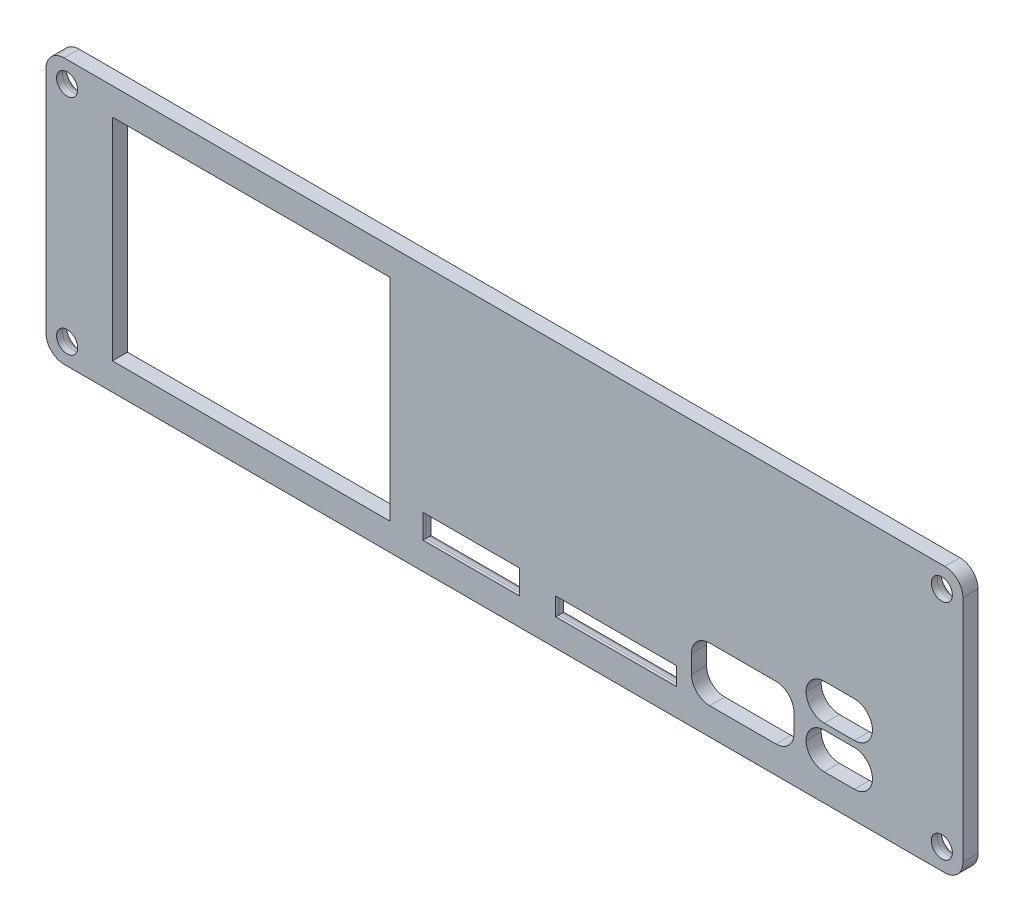
SolidWorks part; units mm, degrees
ref_plane "Front Plane" through (0, 0, 0) normal (0, 0, 1) x (1, 0, 0)
ref_plane "Top Plane" through (0, 0, 0) normal (0, 1, 0) x (1, 0, 0)
ref_plane "Right Plane" through (0, 0, 0) normal (1, 0, 0) x (0, 0, -1)
sketch "Sketch1" plane through (0, 0, 0) normal (0, 0, 1) x (1, 0, 0)
  line L1 (76, -22) -> (-76, -22)
  line L2 (76, -22) -> (76, 22)
  line L3 (76, 22) -> (-76, 22)
  line L4 (-76, -22) -> (-76, 22)
  line L5 (76, -22) -> (-76, 22) construction
  line L6 (76, 22) -> (-76, -22) construction
  point P0 (0, 0)
  dimension "D1" = 152
  dimension "D2" = 44
extrude "main_body" add sketch "Sketch1" along normal blind 2.5
fillet "body_corners" radius 3 4 edges at (-76, -22, 1.25) (76, -22, 1.25) (76, 22, 1.25) (-76, 22, 1.25)
sketch "Sketch2" plane through (0, 0, 2.5) normal (0, 0, 1) x (1, 0, 0)
  line L0 (-76, 18.5) -> (76, 18.5) construction
  line L1 (-76, 19) -> (-76, -19) construction
  line L2 (76, -19) -> (76, 19) construction
  line L3 (-72.5, 22) -> (-72.5, -22) construction
  line L4 (-76, -18.5) -> (76, -18.5) construction
  line L8 (73, 22) -> (-73, 22) construction
  line L9 (72.5, 22) -> (72.5, -22) construction
  line L10 (-73, -22) -> (73, -22) construction
  circle A1 centre (-72.5, -18.5) radius 1.75
  circle A2 centre (72.5, 18.5) radius 1.75
  circle A3 centre (72.5, -18.5) radius 1.75
  circle A4 centre (-72.5, 18.5) radius 1.75
  dimension "D5" = 3.5
  dimension "D6" = 3.5
  dimension "D7" = 3.5
  dimension "D8" = 3.5
  dimension "D1" = 3.5
  dimension "D2" = 3.5
  dimension "D3" = 3.5
  dimension "D4" = 3.5
extrude "mounting_holes" cut sketch "Sketch2" against normal through all
fillet "bolt_heads" radius 1.5 4 edges at (-70.75, -18.5, 0) (-70.75, 18.5, 0) (74.25, -18.5, 0) (74.25, 18.5, 0)
sketch "Sketch3" plane through (0, 0, 2.5) normal (0, 0, 1) x (1, 0, 0)
  line L0 (-76, 5) -> (76, 5) construction
  line L1 (-76, 19) -> (-76, -19) construction
  line L2 (76, -19) -> (76, 19) construction
  line L3 (73, 22) -> (-73, 22) construction
  line L4 (-73, -22) -> (73, -22) construction
  line L5 (0, 22) -> (0, -22) construction
  line L6 (76, -19) -> (76, 19) construction
  line L7 (-65, 17.5) -> (-19, 17.5)
  line L8 (50, -4.5) -> (61, -4.5)
  line L9 (-65, 17.5) -> (-65, -17.5)
  line L10 (50, -4.5) -> (50, -10.5)
  line L11 (50, -10.5) -> (61, -10.5)
  line L12 (-65, -17.5) -> (-19, -17.5)
  line L13 (61, -4.5) -> (61, -10.5)
  line L14 (50, -4.5) -> (61, -10.5) construction
  line L15 (-19, 17.5) -> (-19, -17.5)
  line L16 (50, -10.5) -> (61, -4.5) construction
  line L17 (31, -8.5) -> (48, -8.5)
  line L18 (31, -8.5) -> (31, -17.5)
  line L19 (31, -17.5) -> (48, -17.5)
  line L20 (48, -8.5) -> (48, -17.5)
  line L21 (31, -8.5) -> (48, -17.5) construction
  line L22 (31, -17.5) -> (48, -8.5) construction
  line L23 (50, -11.5) -> (61, -11.5)
  line L24 (50, -11.5) -> (50, -17.5)
  line L25 (50, -17.5) -> (61, -17.5)
  line L26 (61, -11.5) -> (61, -17.5)
  line L27 (50, -11.5) -> (61, -17.5) construction
  line L28 (50, -17.5) -> (61, -11.5) construction
  line L29 (8.5, -14.5) -> (28.5, -14.5)
  line L30 (8.5, -14.5) -> (8.5, -17.5)
  line L31 (8.5, -17.5) -> (28.5, -17.5)
  line L32 (28.5, -14.5) -> (28.5, -17.5)
  line L33 (8.5, -14.5) -> (28.5, -17.5) construction
  line L34 (8.5, -17.5) -> (28.5, -14.5) construction
  line L35 (-13.5, -13.5) -> (2.5, -13.5)
  line L36 (-13.5, -13.5) -> (-13.5, -17.5)
  line L37 (-13.5, -17.5) -> (2.5, -17.5)
  line L38 (2.5, -13.5) -> (2.5, -17.5)
  line L39 (-13.5, -13.5) -> (2.5, -17.5) construction
  line L40 (-13.5, -17.5) -> (2.5, -13.5) construction
  line L41 (-65, 17.5) -> (-19, -17.5) construction
  line L42 (-65, -17.5) -> (-19, 17.5) construction
  line L43 (-76, 19) -> (-76, -19) construction
  line L44 (-73, -22) -> (73, -22) construction
  point P12 (-42, 0)
  point P15 (-5.5, -15.5)
  point P34 (55.5, -14.5)
  point P36 (55.5, -7.5)
  point P41 (39.5, -13)
  point P49 (55.5, -17.5)
  point P51 (18.5, -16)
  dimension "D7" = 73.5
  dimension "D8" = 4.5
  dimension "D9" = 4
  dimension "D10" = 16
  dimension "D11" = 46
  dimension "D12" = 47.5
  dimension "D13" = 6
  dimension "D14" = 11
  dimension "D15" = 28
  dimension "D1" = 17
  dimension "D4" = 11
  dimension "D5" = 4.5
  dimension "D6" = 35
  dimension "D16" = 4.5
  dimension "D17" = 15
  dimension "D18" = 15
  dimension "D19" = 11
  dimension "D20" = 6
  dimension "D21" = 17
  dimension "D22" = 9
  dimension "D25" = 11.5
  dimension "D26" = 4.5
  dimension "D28" = 4.5
  dimension "D30" = 3
  dimension "D31" = 20
extrude "connectors" cut sketch "Sketch3" against normal through all
fillet "usb_host_corners" radius 3 4 edges at (48, -17.5, 1.25) (48, -8.5, 1.25) (31, -17.5, 1.25) (31, -8.5, 1.25)
fillet "usb_dfu_corners" radius 3 8 edges at (61, -4.5, 1.25) (61, -10.5, 1.25) (50, -10.5, 1.25) (50, -4.5, 1.25) (61, -11.5, 1.25) (61, -17.5, 1.25) (50, -17.5, 1.25) (50, -11.5, 1.25)
fillet "Fillet1" radius 2 8 edges at (-5.5, -13.5, 0) (-13.5, -15.5, 0) (-5.5, -17.5, 0) (2.5, -15.5, 0) (8.5, -16, 0) (28.5, -16, 0) (18.5, -17.5, 0) (18.5, -14.5, 0)
